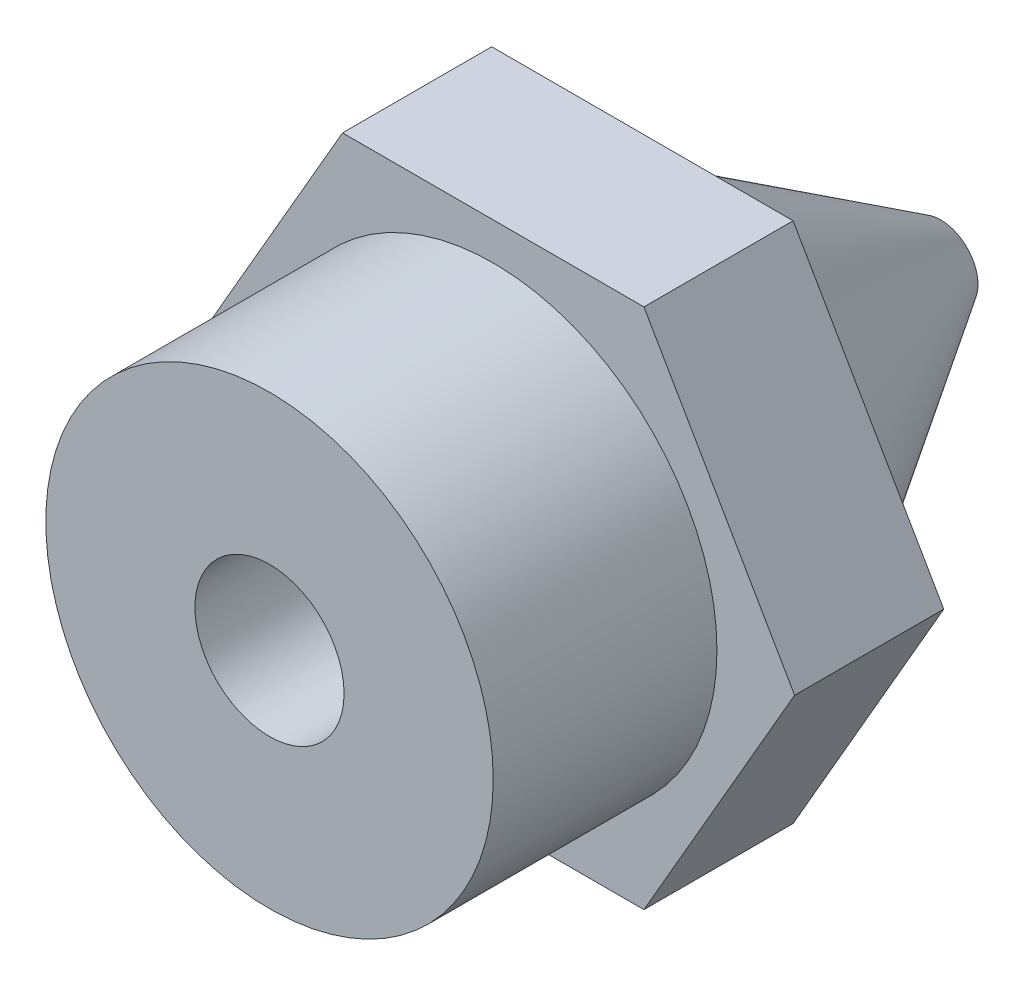
SolidWorks part; units mm, degrees
ref_plane "Plan de face" through (0, 0, 0) normal (0, 0, 1) x (1, 0, 0)
ref_plane "Plan de dessus" through (0, 0, 0) normal (0, 1, 0) x (1, 0, 0)
ref_plane "Plan de droite" through (0, 0, 0) normal (1, 0, 0) x (0, 0, -1)
sketch "Esquisse1" plane through (0, 0, 0) normal (0, 0, 1) x (1, 0, 0)
  line L1 (4.0415, 0) -> (2.0207, 3.5)
  line L2 (2.0207, 3.5) -> (-2.0207, 3.5)
  line L3 (-2.0207, 3.5) -> (-4.0415, 0)
  line L4 (-4.0415, 0) -> (-2.0207, -3.5)
  line L5 (-2.0207, -3.5) -> (2.0207, -3.5)
  line L6 (2.0207, -3.5) -> (4.0415, 0)
  circle A0 centre (0, 0) radius 3.5 construction
  dimension "D1" = 7
extrude "Boss.-Extru.1" add sketch "Esquisse1" along normal blind 9
sketch "Esquisse2" plane through (0, 0, 9) normal (0, 0, 1) x (1, 0, 0)
  line L1 (-7.9912, 5.5023) -> (7.566, 5.5023)
  line L2 (-7.9912, 5.5023) -> (-7.9912, -5.9665)
  line L3 (-7.9912, -5.9665) -> (7.566, -5.9665)
  line L4 (7.566, 5.5023) -> (7.566, -5.9665)
  circle A0 centre (0, 0) radius 3
  dimension "D1" = 6
extrude "Enlèv. mat.-Extru.1" cut sketch "Esquisse2" against normal blind 3
cosmetic thread "Représentation de filetage1" parameters "D2"=4.891
sketch "Esquisse3" plane through (0, 0, 0) normal (0, 0, -1) x (-1, 0, 0)
  line L1 (7.8656, -6.0768) -> (-7.4574, -6.0768)
  line L2 (7.8656, -6.0768) -> (7.8656, 5.7844)
  line L3 (7.8656, 5.7844) -> (-7.4574, 5.7844)
  line L4 (-7.4574, -6.0768) -> (-7.4574, 5.7844)
  circle A0 centre (0, 0) radius 3
  dimension "D1" = 6
extrude "Enlèv. mat.-Extru.3" cut sketch "Esquisse3" against normal blind 4
chamfer "Chanfrein2" distance 4 angle 32 1 edges at (-3, 0, 0) first distance on face at (-3, 0, 4)
sketch "Esquisse4" plane through (0, 0, 0) normal (0, 1, 0) x (1, 0, 0)
  line L0 (0, 0) -> (0, -9) construction
  line L1 (0.5005, 0) -> (-0.5005, 0) construction
  line L2 (-3, -9) -> (3, -9) construction
  line L3 (0, 0) -> (0.2, 0) construction
  line L4 (0, 1.4) -> (1, -6.6) construction
  line L5 (0, 0) -> (0, 1.4) construction
  line L6 (0.2, 0) -> (0.2, -1.4) construction
  line L7 (0.2, -1.4) -> (0, -1.4) construction
  line L8 (0, 1.4) -> (1, -6.6)
  line L9 (1, -6.6) -> (1, -9)
  line L10 (1, -9) -> (0, -9)
  line L11 (0, -9) -> (0, 1.4)
  dimension "D1" = 8
  dimension "D2" = 1
revolve "Enlèvement de matière-Révolution1" cut sketch "Esquisse4" angle 360 about L11
chamfer "Chanfrein3" [suppressed] distance 0.25 angle 30
